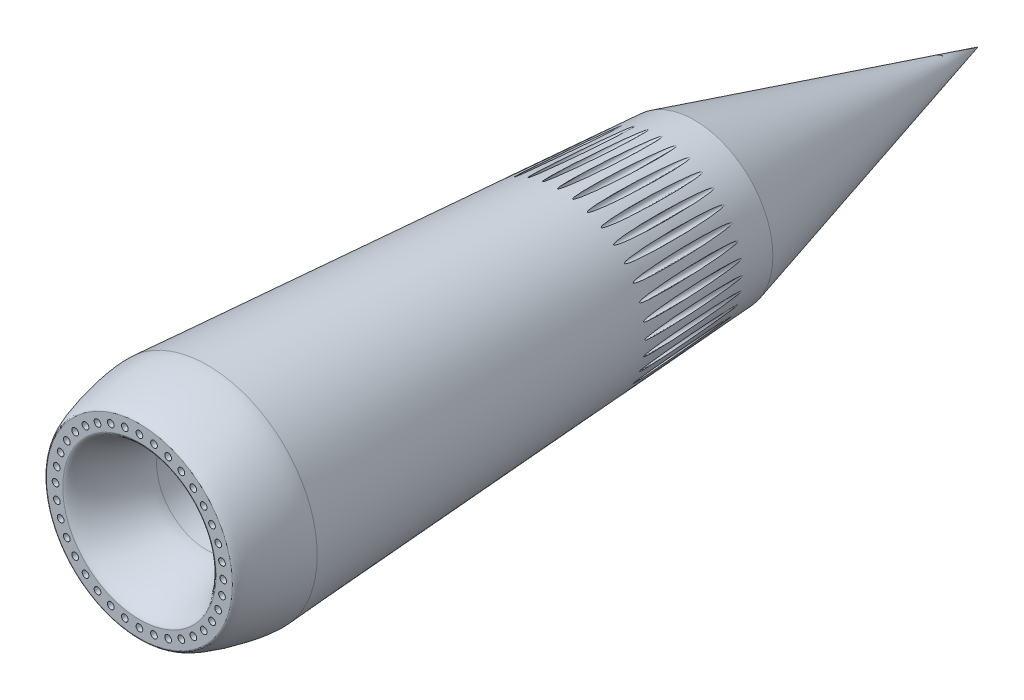
SolidWorks part; units mm, degrees
ref_plane "Front Plane" through (0, 0, 0) normal (0, 0, 1) x (1, 0, 0)
ref_plane "Top Plane" through (0, 0, 0) normal (0, 1, 0) x (1, 0, 0)
ref_plane "Right Plane" through (0, 0, 0) normal (1, 0, 0) x (0, 0, -1)
sketch "Sketch1" plane through (0, 0, 0) normal (0, 0, 1) x (1, 0, 0)
  circle A1 centre (0, 0) radius 3.5 construction
  circle A39 centre (-1.607, 1.9151) radius 0.1
  circle A40 centre (-1.25, 2.1651) radius 0.1
  circle A41 centre (-0.8551, 2.3492) radius 0.1
  circle A42 centre (-0.4341, 2.462) radius 0.1
  circle A43 centre (0, 2.5) radius 0.1
  circle A44 centre (0.4341, 2.462) radius 0.1
  circle A45 centre (0.8551, 2.3492) radius 0.1
  circle A46 centre (1.25, 2.1651) radius 0.1
  circle A47 centre (1.607, 1.9151) radius 0.1
  circle A48 centre (1.9151, 1.607) radius 0.1
  circle A49 centre (2.1651, 1.25) radius 0.1
  circle A50 centre (2.3492, 0.8551) radius 0.1
  circle A51 centre (2.462, 0.4341) radius 0.1
  circle A52 centre (2.3492, -0.8551) radius 0.1
  circle A53 centre (2.462, -0.4341) radius 0.1
  circle A54 centre (1.25, -2.1651) radius 0.1
  circle A55 centre (1.607, -1.9151) radius 0.1
  circle A56 centre (1.9151, -1.607) radius 0.1
  circle A57 centre (2.1651, -1.25) radius 0.1
  circle A58 centre (2.5, 0) radius 0.1
  circle A59 centre (0.4341, -2.462) radius 0.1
  circle A60 centre (0.8551, -2.3492) radius 0.1
  circle A61 centre (-0.4341, -2.462) radius 0.1
  circle A62 centre (-0.8551, -2.3492) radius 0.1
  circle A63 centre (0, -2.5) radius 0.1
  circle A64 centre (-1.25, -2.1651) radius 0.1
  circle A65 centre (-1.9151, -1.607) radius 0.1
  circle A66 centre (-1.607, -1.9151) radius 0.1
  circle A67 centre (-2.462, -0.4341) radius 0.1
  circle A68 centre (-2.3492, -0.8551) radius 0.1
  circle A69 centre (-2.1651, -1.25) radius 0.1
  circle A70 centre (-2.3492, 0.8551) radius 0.1
  circle A71 centre (-2.462, 0.4341) radius 0.1
  circle A72 centre (-2.5, 0) radius 0.1
  circle A73 centre (-1.9151, 1.607) radius 0.1
  circle A74 centre (-2.1651, 1.25) radius 0.1
  circle A76 centre (0, 0) radius 1.4874
  point P3 (0, 0)
  point P5 (0, 0)
  point P8 (0, 0)
  point P10 (0, 0)
  point P79 (0, 0)
  point P151 (0, 0)
  point P152 (0, 0)
  point P153 (0, 0)
  point P154 (0, 0)
  point P155 (0, 0)
  point P156 (0, 0)
  point P157 (0, 0)
  point P158 (0, 0)
  point P159 (0, 0)
  point P160 (0, 0)
  point P161 (0, 0)
  point P162 (0, 0)
  point P163 (0, 0)
  point P164 (0, 0)
  point P165 (0, 0)
  point P166 (0, 0)
  point P167 (0, 0)
  point P168 (0, 0)
  point P169 (0, 0)
  point P170 (0, 0)
  point P171 (0, 0)
  point P172 (0, 0)
  point P173 (0, 0)
  point P174 (0, 0)
  point P175 (0, 0)
  point P176 (0, 0)
  point P177 (0, 0)
  point P178 (0, 0)
  point P179 (0, 0)
  point P180 (0, 0)
  point P181 (0, 0)
  point P182 (0, 0)
  point P183 (0, 0)
  point P184 (0, 0)
  point P185 (0, 0)
  point P186 (0, 0)
  point P187 (0, 0)
  point P188 (0, 0)
  point P189 (0, 0)
  point P190 (0, 0)
  point P191 (0, 0)
  point P192 (0, 0)
  point P193 (0, 0)
  point P194 (0, 0)
  point P195 (0, 0)
  point P196 (0, 0)
  point P197 (-3.9814, -9.5644)
  point P198 (0, 0)
  point P199 (-3.9815, -9.5644)
  dimension "D2" = 7
sketch "Sketch2" plane through (0, 0, 0) normal (1, 0, 0) x (0, 0, -1)
  line L0 (0, 0) -> (15, 0) construction
sketch "Sketch3" plane through (0, 0, 0) normal (1, 0, 0) x (0, 0, -1)
  line L0 (0, 0) -> (25, 0)
  line L1 (0, 1.4874) -> (0, -1.4874) construction
  line L3 (0, 3.5) -> (0, -3.5) construction
  line L4 (0, -3.4) -> (0, 0)
  line L5 (0, -3.4) -> (16.5463, -2.3383)
  line L6 (16.5463, -2.3383) -> (25, 0)
  point P4 (17.4581, -2.3442)
  point P5 (7.2598, -2.581)
  point P9 (0, 0)
  point P10 (8.2021, -1.8958)
  point P11 (0, 0)
  point P13 (0, 0)
  point P14 (0, 0)
  point P15 (0, 0)
  point P16 (8.3445, -1.7571)
  point P17 (13.7094, 0)
  point P18 (12.5311, 0)
  point P19 (0, 0)
  point P20 (9.0792, -1.8195)
  point P21 (9.8172, -1.6067)
  point P22 (10.5667, -1.303)
  point P23 (16.6713, 0)
  point P24 (14.6022, -1.1701)
  point P25 (13.9275, -2.2962)
  point P26 (11.0326, -2.8857)
  point P27 (11.8827, -2.4026)
  point P28 (11.078, -2.0535)
  point P29 (14.6014, -1.3139)
  point P30 (0, 0)
  point P31 (14.8029, -2.4803)
  point P32 (16.5463, -2.3383)
revolve "Revolve1" add sketch "Sketch3" angle 360 about L0
extrude "Cut-Extrude5" cut sketch "Sketch1" against normal blind 18
fillet "Fillet9" radius 2 1 edges at (3.4, 0, 0) second distance 0.5 conic rho 0.2 first distance on face at (2.0149, -1.6, -12.8911)
fillet "Fillet10" radius 0.8 1 edges at (1.4874, 0, 0) second distance 2 conic rho 0.2
